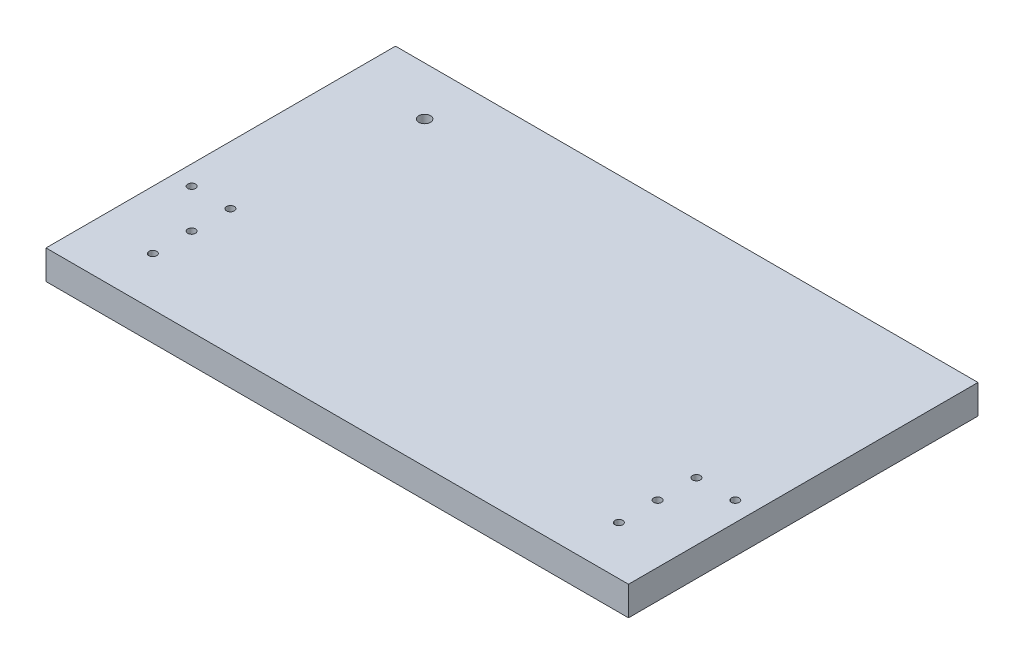
SolidWorks part; units mm, degrees
ref_plane "Alzado" through (0, 0, 0) normal (0, 0, 1) x (1, 0, 0)
ref_plane "Planta" through (0, 0, 0) normal (0, 1, 0) x (1, 0, 0)
ref_plane "Vista lateral" through (0, 0, 0) normal (1, 0, 0) x (0, 0, -1)
sketch "Croquis1" plane through (0, 0, 0) normal (0, 1, 0) x (1, 0, 0)
  line L1 (-150, -90) -> (150, -90)
  line L2 (-150, -90) -> (-150, 90)
  line L3 (-150, 90) -> (150, 90)
  line L4 (150, -90) -> (150, 90)
  line L5 (-150, -90) -> (150, 90) construction
  line L6 (-150, 90) -> (150, -90) construction
  point P0 (0, 0)
  dimension "D1" = 300
  dimension "D2" = 180
extrude "Saliente-Extruir1" add sketch "Croquis1" along normal blind 15
sketch "Croquis2" plane through (0, 15, 0) normal (0, 1, 0) x (1, 0, 0)
  line L1 (-150, -90) -> (150, -90) construction
  line L2 (-150, 90) -> (-150, -90) construction
  line L3 (150, -90) -> (150, 90) construction
  circle A0 centre (-120, -65) radius 2
  circle A1 centre (-120, -45) radius 2
  circle A2 centre (120, -65) radius 2
  circle A3 centre (120, -45) radius 2
  circle A4 centre (-140, -25) radius 2
  circle A5 centre (-120, -25) radius 2
  circle A6 centre (120, -25) radius 2
  circle A7 centre (140, -25) radius 2
  dimension "D1" = 25
  dimension "D2" = 0
  dimension "D3" = 25
  dimension "D4" = 0
  dimension "D7" = 10
  dimension "D8" = 20
  dimension "D9" = 30
  dimension "D10" = 10
  dimension "D5" = 30
  dimension "D6" = 30
  dimension "D11" = 65
  dimension "D12" = 0
  dimension "D13" = 65
  dimension "D14" = 0
  dimension "D15" = 45
  dimension "D16" = 45
extrude "Cortar-Extruir1" cut sketch "Croquis2" against normal blind 10
sketch "Croquis3" plane through (0, 0, 0) normal (0, -1, 0) x (1, 0, 0)
  line L0 (150, -90) -> (-150, -90) construction
  line L1 (-150, -90) -> (-150, 90) construction
  circle A0 centre (-140, -65) radius 2
  dimension "D1" = 25
  dimension "D2" = 10
extrude "Cortar-Extruir2" cut sketch "Croquis3" against normal blind 10
sketch "Croquis4" plane through (0, 0, 0) normal (0, -1, 0) x (1, 0, 0)
  line L0 (-150, -90) -> (-150, 90) construction
  circle A0 centre (-110, -65) radius 3
  dimension "D1" = 40
extrude "Cortar-Extruir3" cut sketch "Croquis4" against normal up to surface (15 mm away) up to face at (140, 15, 27)
